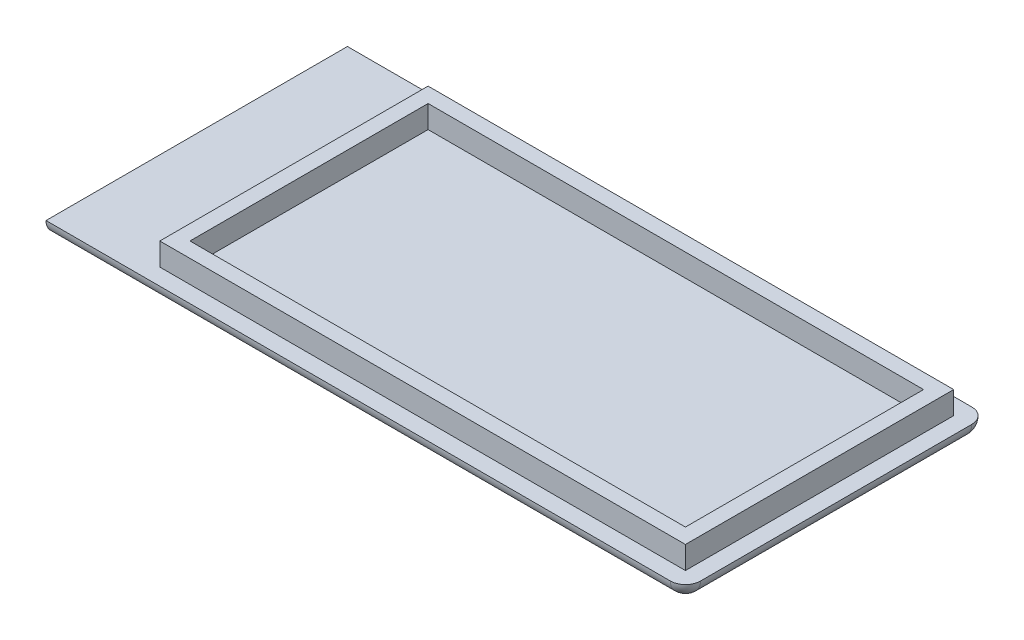
SolidWorks part; units mm, degrees
ref_plane "Front Plane" through (0, 0, 0) normal (0, 0, 1) x (1, 0, 0)
ref_plane "Top Plane" through (0, 0, 0) normal (0, 1, 0) x (1, 0, 0)
ref_plane "Right Plane" through (0, 0, 0) normal (1, 0, 0) x (0, 0, -1)
sketch "Sketch1" plane through (0, 0, 0) normal (0, 0, 1) x (1, 0, 0)
  line L1 (0, 0) -> (42.4256, 0)
  line L2 (0, 0) -> (0, 1)
  line L3 (0, 1) -> (42.4256, 1)
  line L4 (42.4256, 0) -> (42.4256, 1)
  dimension "D1" = 1
  dimension "D2" = 42.4256
extrude "Boss-Extrude1" add sketch "Sketch1" along normal blind 20
fillet "Fillet1" radius 1 3 edges at (42.4256, 0, 10) (21.2128, 0, 0) (21.2128, 0, 20)
sketch "Sketch2" plane through (0, 1, 0) normal (0, 1, 0) x (1, 0, 0)
  line L0 (7.4514, -2.1) -> (7.4514, -17.9)
  line L1 (6.4514, -1.1) -> (41.3256, -1.1)
  line L2 (6.4514, -1.1) -> (6.4514, -18.9)
  line L3 (6.4514, -18.9) -> (41.3256, -18.9)
  line L4 (41.3256, -1.1) -> (41.3256, -18.9)
  line L5 (7.4514, -17.9) -> (40.3256, -17.9)
  line L6 (40.3256, -2.1) -> (40.3256, -17.9)
  line L7 (7.4514, -2.1) -> (40.3256, -2.1)
  line L8 (41.4256, 0) -> (0, 0) construction
  line L9 (42.4256, -19) -> (42.4256, -1) construction
  line L10 (0, -20) -> (41.4256, -20) construction
  dimension "D2" = 1.1
  dimension "D3" = 1.1
  dimension "D4" = 1.1
  dimension "D5" = 34.8742
  dimension "D1" = 1
extrude "Boss-Extrude2" add sketch "Sketch2" along normal blind 1.5
